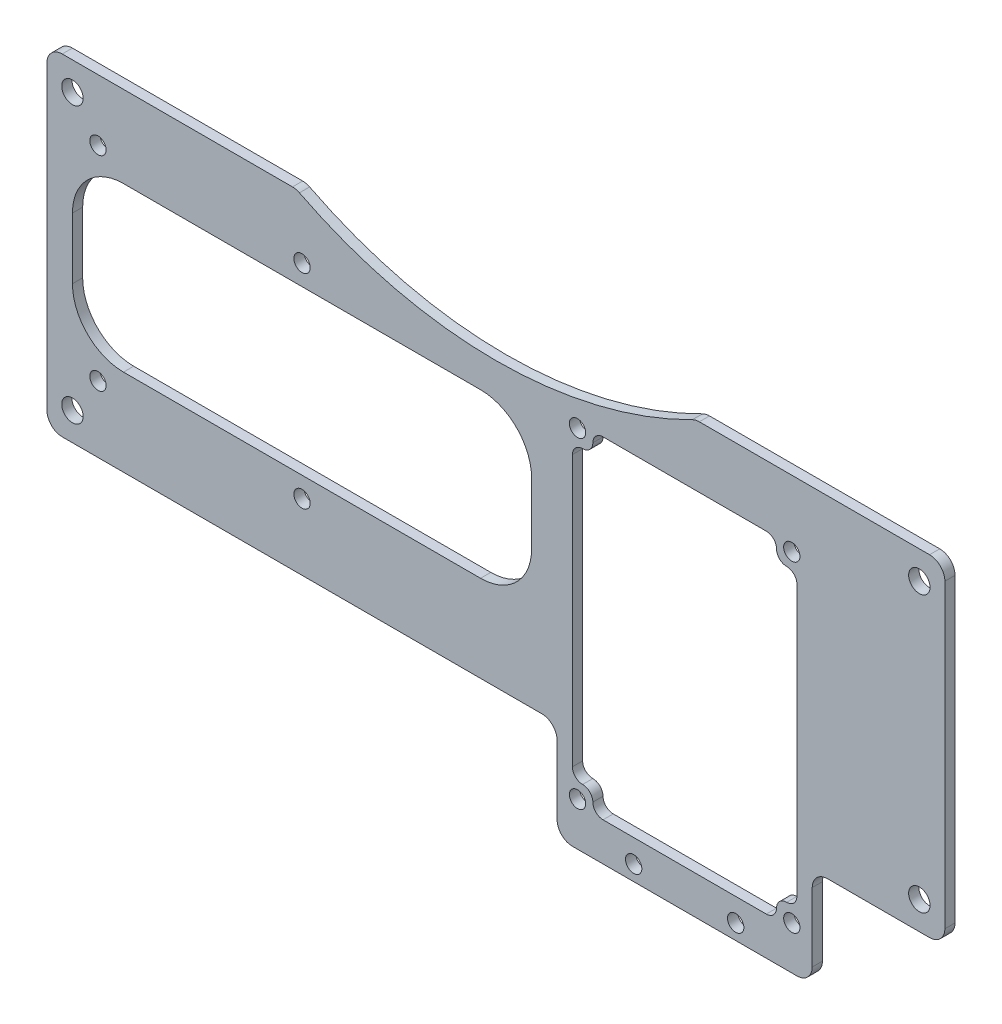
SolidWorks part; units mm, degrees
material "Thornel Mat VMA"
ref_plane "前视基准面" through (0, 0, 0) normal (0, 0, 1) x (1, 0, 0)
ref_plane "上视基准面" through (0, 0, 0) normal (0, 1, 0) x (1, 0, 0)
ref_plane "右视基准面" through (0, 0, 0) normal (1, 0, 0) x (0, 0, -1)
other "Configuration Table"
sketch "草图1" plane through (0, 0, 0) normal (0, 0, 1) x (1, 0, 0)
  line L0 (-88, 0) -> (88, 0) construction
  line L1 (88, -32.5) -> (-88, -32.5)
  line L2 (88, -32.5) -> (88, 32.5)
  line L3 (88, 32.5) -> (-88, 32.5)
  line L4 (-88, -32.5) -> (-88, 32.5)
  line L5 (88, -32.5) -> (-88, 32.5) construction
  line L6 (88, 32.5) -> (-88, -32.5) construction
  line L7 (0, 32.5) -> (0, -32.5) construction
  line L8 (-83, 32.5) -> (-83, -32.5) construction
  line L9 (83, 32.5) -> (83, -32.5) construction
  circle A0 centre (-83, 27) radius 2.1
  circle A1 centre (-83, -27) radius 2.1
  circle A2 centre (83, -27) radius 2.1
  circle A3 centre (83, 27) radius 2.1
  point P0 (0, 0)
  dimension "D3" = 27
  dimension "D4" = 4.2
  dimension "D5" = 4.2
  dimension "D6" = 27
  dimension "D1" = 65
  dimension "D2" = 176
  dimension "D7" = 166
extrude "凸台-拉伸1" add sketch "草图1" along normal blind 2
fillet "圆角1" radius 3 4 edges at (88, 32.5, 1) (88, -32.5, 1) (-88, -32.5, 1) (-88, 32.5, 1)
sketch "草图2" plane through (0, 0, 2) normal (0, 0, 1) x (1, 0, 0)
  line L0 (85, 32.5) -> (-85, 32.5) construction
  circle A0 centre (0, 107.95) radius 85
  dimension "D1" = 75.45
  dimension "D2" = 170
extrude "切除-拉伸1" cut sketch "草图2" against normal blind 24
sketch "草图4" plane through (0, 0, 2) normal (0, 0, 1) x (1, 0, 0)
  line L0 (-85, -32.5) -> (85, -32.5) construction
  line L1 (12, -32.5) -> (62, -32.5)
  line L2 (12, -32.5) -> (12, -52)
  line L3 (12, -52) -> (62, -52)
  line L4 (62, -32.5) -> (62, -52)
  line L5 (-88, 29.5) -> (-88, -29.5) construction
  dimension "D1" = 100
  dimension "D2" = 50
  dimension "D3" = 19.5
extrude "凸台-拉伸2" add sketch "草图4" against normal blind 2
fillet "圆角2" radius 3 6 edges at (12, -52, 1) (62, -52, 1) (62, -32.5, 1) (39.1446, 32.5, 1) (-39.1446, 32.5, 1) (12, -32.5, 1)
sketch "草图3" plane through (0, 0, 2) normal (0, 0, 1) x (1, 0, 0)
  line L0 (-39.8698, 32.5) -> (-85, 32.5) construction
  line L1 (58, -43.5) -> (16, -43.5) construction
  line L2 (58, -43.5) -> (58, 19.5) construction
  line L3 (58, 19.5) -> (16, 19.5) construction
  line L4 (16, -43.5) -> (16, 19.5) construction
  line L5 (58, -43.5) -> (16, 19.5) construction
  line L6 (58, 19.5) -> (16, -43.5) construction
  line L8 (-88, 29.5) -> (-88, -29.5) construction
  line L9 (19, 20.5) -> (19, 16.5)
  line L10 (19, 16.5) -> (15, 16.5)
  line L11 (15, 16.5) -> (15, -40.5)
  line L12 (15, -40.5) -> (19, -40.5)
  line L13 (19, -40.5) -> (19, -44.5)
  line L14 (19, -44.5) -> (55, -44.5)
  line L15 (55, -44.5) -> (55, -40.5)
  line L16 (55, -40.5) -> (59, -40.5)
  line L17 (59, -40.5) -> (59, 16.5)
  line L18 (59, 16.5) -> (55, 16.5)
  line L19 (55, 16.5) -> (55, 20.5)
  line L20 (55, 20.5) -> (19, 20.5)
  line L21 (88, -29.5) -> (88, 29.5) construction
  line L22 (85, 32.5) -> (39.8698, 32.5) construction
  line L23 (15, -52) -> (59, -52) construction
  circle A1 centre (16, 19.5) radius 1.6
  circle A2 centre (58, 19.5) radius 1.6
  circle A3 centre (58, -43.5) radius 1.6
  circle A4 centre (16, -43.5) radius 1.6
  point P0 (37, -12)
  point P29 (37, -44.5)
  dimension "D3" = 3.2
  dimension "D1" = 42
  dimension "D2" = 63
  dimension "D4" = 13
  dimension "D5" = 104
  dimension "D6" = 3
  dimension "D7" = 3
  dimension "D8" = 3
  dimension "D9" = 3
  dimension "D10" = 3
  dimension "D11" = 3
  dimension "D12" = 3
  dimension "D13" = 3
  dimension "D14" = 29
  dimension "D15" = 103
  dimension "D16" = 12
  dimension "D17" = 7.5
extrude "切除-拉伸2" cut sketch "草图3" against normal blind 12
fillet "圆角3" radius 2 12 edges at (55, 16.5, 1) (59, 16.5, 1) (59, -40.5, 1) (55, -40.5, 1) (55, -44.5, 1) (19, -44.5, 1) (19, -40.5, 1) (15, -40.5, 1) (19, 16.5, 1) (19, 20.5, 1) (55, 20.5, 1) (15, 16.5, 1)
sketch "草图5" plane through (0, 0, 2) normal (0, 0, 1) x (1, 0, 0)
  line L0 (12, -49) -> (62, -49) construction
  line L3 (12, -35.5) -> (12, -49) construction
  line L4 (62, -49) -> (62, -35.5) construction
  line L5 (15, -52) -> (59, -52) construction
  line L6 (62, -49) -> (62, -35.5) construction
  circle A1 centre (27, -49) radius 1.6
  circle A2 centre (47, -49) radius 1.6
  dimension "D2" = 3.2
  dimension "D3" = 20
  dimension "D4" = 15
  dimension "D1" = 3
extrude "切除-拉伸3" cut sketch "草图5" against normal blind 12
sketch "草图6" plane through (0, 0, 2) normal (0, 0, 1) x (1, 0, 0)
  line L1 (-78, 20.5) -> (-38, 20.5) construction
  line L2 (-78, 20.5) -> (-78, -19.5) construction
  line L3 (-78, -19.5) -> (-38, -19.5) construction
  line L4 (-38, 20.5) -> (-38, -19.5) construction
  line L5 (-88, 29.5) -> (-88, -29.5) construction
  line L6 (-39.8698, 32.5) -> (-85, 32.5) construction
  circle A0 centre (-78, 20.5) radius 1.6
  circle A1 centre (-38, 20.5) radius 1.6
  circle A2 centre (-38, -19.5) radius 1.6
  circle A3 centre (-78, -19.5) radius 1.6
  dimension "D5" = 3.2
  dimension "D1" = 40
  dimension "D2" = 40
  dimension "D3" = 10
  dimension "D4" = 12
extrude "切除-拉伸4" cut sketch "草图6" against normal blind 12
sketch "草图7" plane through (0, 0, 2) normal (0, 0, 1) x (1, 0, 0)
  line L0 (-88, 29.5) -> (-88, -29.5) construction
  line L1 (-83, 16.5) -> (7, 16.5)
  line L2 (-83, 16.5) -> (-83, -15.5)
  line L3 (-83, -15.5) -> (7, -15.5)
  line L4 (7, 16.5) -> (7, -15.5)
  line L5 (-85, -32.5) -> (9, -32.5) construction
  dimension "D1" = 32
  dimension "D2" = 90
  dimension "D3" = 5
  dimension "D4" = 17
extrude "切除-拉伸5" cut sketch "草图7" against normal blind 10
fillet "圆角4" radius 10 4 edges at (7, 16.5, 1) (7, -15.5, 1) (-83, -15.5, 1) (-83, 16.5, 1)
